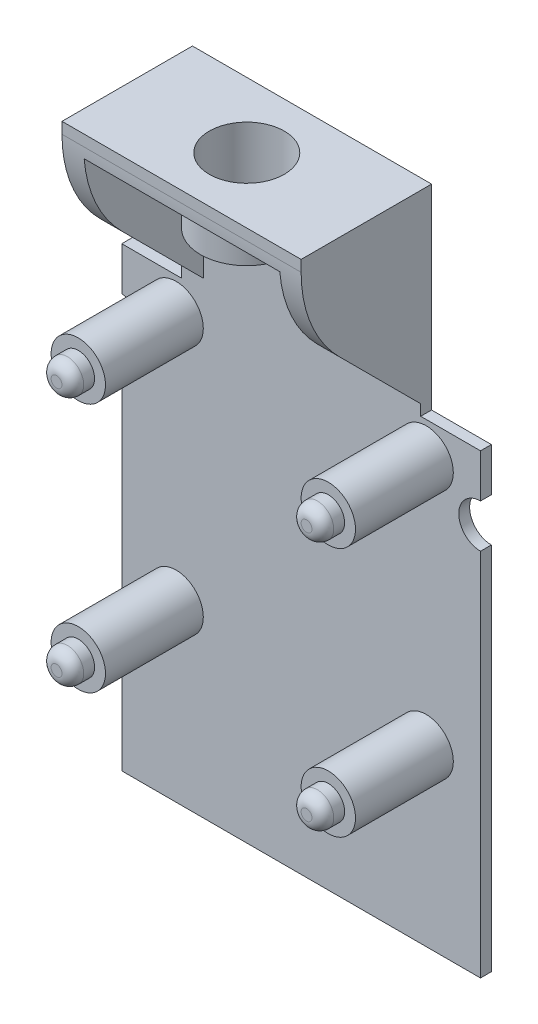
SolidWorks part; units mm, degrees
ref_plane "Ebene vorne" through (0, 0, 0) normal (0, 0, 1) x (1, 0, 0)
ref_plane "Ebene oben" through (0, 0, 0) normal (0, 1, 0) x (1, 0, 0)
ref_plane "Ebene rechts" through (0, 0, 0) normal (1, 0, 0) x (0, 0, -1)
sketch "Skizze1" plane through (0, 0, 0) normal (0, 0, 1) x (1, 0, 0)
  line L0 (0, -30) -> (0, 30) construction
  line L1 (-16.5, 30) -> (16.5, 30)
  line L2 (-16.5, 30) -> (-16.5, -30)
  line L3 (-16.5, -30) -> (16.5, -30)
  line L4 (16.5, 30) -> (16.5, -30)
  line L5 (-16.5, 30) -> (16.5, -30) construction
  line L6 (-16.5, -30) -> (16.5, 30) construction
  line L7 (-16.5, 30) -> (-11, 30)
  line L8 (-16.5, 30) -> (-16.5, 12)
  line L9 (-16.5, 12) -> (-11, 12)
  line L10 (-11, 30) -> (-11, 12)
  line L11 (16.5, 30) -> (11, 30)
  line L12 (16.5, 30) -> (16.5, 12)
  line L13 (16.5, 12) -> (11, 12)
  line L14 (11, 30) -> (11, 12)
  line L15 (-11, 30) -> (11, 30)
  line L16 (-11, 30) -> (-11, 28)
  line L17 (-11, 28) -> (11, 28)
  line L18 (11, 30) -> (11, 28)
  line L19 (-11, 28) -> (-9, 28)
  line L20 (-11, 28) -> (-11, 12)
  line L21 (-11, 12) -> (-9, 12)
  line L22 (-9, 28) -> (-9, 12)
  line L23 (11, 28) -> (9, 28)
  line L24 (11, 28) -> (11, 12)
  line L25 (11, 12) -> (9, 12)
  line L26 (9, 28) -> (9, 12)
  line L28 (-11.5, 9) -> (11.5, 9) construction
  line L29 (-11.5, 9) -> (-11.5, -14) construction
  line L30 (-11.5, -14) -> (11.5, -14) construction
  line L31 (11.5, 9) -> (11.5, -14) construction
  line L32 (-11.5, 9) -> (11.5, -14) construction
  line L33 (-11.5, -14) -> (11.5, 9) construction
  circle A0 centre (-11.5, 9) radius 1.5
  circle A1 centre (11.5, 9) radius 1.5
  circle A2 centre (11.5, -14) radius 1.5
  circle A3 centre (-11.5, -14) radius 1.5
  circle A4 centre (-11.5, 9) radius 2.5
  circle A5 centre (11.5, 9) radius 2.5
  circle A6 centre (11.5, -14) radius 2.5
  circle A7 centre (-11.5, -14) radius 2.5
  arc A8 (-16.5, 8) -> (-16.5, 4) centre (-16.5, 6) cw
  arc A9 (16.5, 8) -> (16.5, 4) centre (16.5, 6) ccw
  point P0 (0, 0)
  point P18 (0, -2.5)
  point P21 (0, 0)
  dimension "D11" = 3
  dimension "D12" = 3
  dimension "D13" = 3
  dimension "D14" = 3
  dimension "D17" = 2
  dimension "D1" = 33
  dimension "D2" = 60
  dimension "D3" = 5.5
  dimension "5" = 5.5
  dimension "D4" = 18
  dimension "D5" = 0
  dimension "D6" = 2
  dimension "D7" = 2
  dimension "D8" = 2
  dimension "D9" = 23
  dimension "D10" = 23
  dimension "D15" = 21
  dimension "24,5" = 24
  dimension "D16" = 1
extrude "Aufsatz-Linear austragen4" add sketch "Skizze1" along normal blind 1 contours L26 L17 L22 L21 L9 L2 L3 L4 L13 L25 A7 A6 A5 A4 region at (0, -4.1652, 0)
extrude "Aufsatz-Linear austragen5" add sketch "Skizze1<3>" along normal blind 10 contours A5 A1 | A4 A0 | A7 A3 | A6 A2 region at (-13.9293, 9, 0) region at (9.0707, 9, 0) region at (9.0707, -14, 0) region at (-13.9293, -14, 0)
sketch "Skizze1<3>" plane through (0, 0, 0) normal (0, 0, 1) x (1, 0, 0) same geometry as "Skizze1"
extrude "Aufsatz-Linear austragen6" add sketch "Skizze1<4>" along normal blind 12 contours A0 | A1 | A3 | A2 region at (-11.5, 9, 0) region at (11.5, 9, 0) region at (11.5, -14, 0) region at (-11.5, -14, 0)
sketch "Skizze1<4>" plane through (0, 0, 0) normal (0, 0, 1) x (1, 0, 0) same geometry as "Skizze1"
fillet "Verrundung4" radius 1 4 edges at (13, -14, 12) (-10, -14, 12) (13, 9, 12) (-10, 9, 12)
extrude "Aufsatz-Linear austragen7" add sketch "Skizze1<5>" along normal blind 12 contours L22 L17 L10 L21 | L10 L17 L14 L1 | L17 L26 L25 L14 region at (0, 29, 0) region at (-10, 20, 0) region at (10, 20, 0)
sketch "Skizze1<5>" plane through (0, 0, 0) normal (0, 0, 1) x (1, 0, 0) same geometry as "Skizze1"
chamfer "Fase3" distance 12 angle 45 2 edges at (-10, 12, 12) (10, 12, 12)
fillet "Verrundung5" radius 12 1 edges at (-10, 24, 12)
ref_plane "Ebene1" through (0, 30, 0) normal (0, 1, 0) x (1, 0, 0)
sketch "Skizze5" plane through (0, 30, 0) normal (0, 1, 0) x (1, 0, 0)
  line L0 (0, 0) -> (0, -12) construction
  line L1 (-11, 0) -> (11, 0) construction
  line L2 (-11, -12) -> (11, -12) construction
  circle A0 centre (0, -6) radius 3.45
  circle A1 centre (0, -6) radius 4.25
  dimension "D1" = 8.5
  dimension "D2" = 6.9
extrude "Schnitt-Linear austragen2" cut sketch "Skizze5" against normal blind 12 contours L0 A0 | A0 L0 region at (1.4642, 30, 6) region at (-1.4642, 30, 6)
extrude "Aufsatz-Linear austragen10" add sketch "Skizze5<4>" against normal blind 6
sketch "Skizze5<4>" plane through (0, 30, 0) normal (0, 1, 0) x (1, 0, 0) same geometry as "Skizze5"
